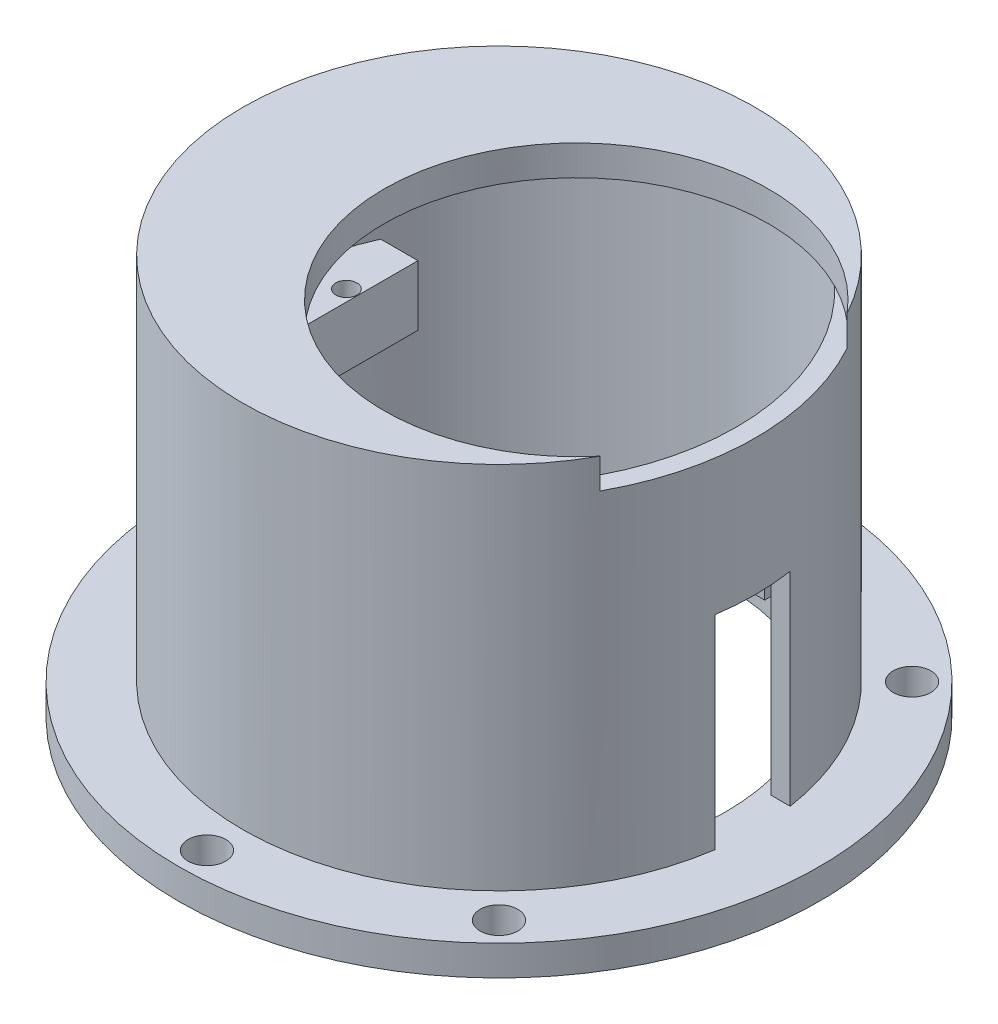
SolidWorks part; units mm, degrees
ref_plane "Front Plane" through (0, 0, 0) normal (0, 0, 1) x (1, 0, 0)
ref_plane "Top Plane" through (0, 0, 0) normal (0, 1, 0) x (1, 0, 0)
ref_plane "Right Plane" through (0, 0, 0) normal (1, 0, 0) x (0, 0, -1)
sketch "Sketch1" plane through (0, 0, 0) normal (0, 1, 0) x (1, 0, 0)
  circle A0 centre (0, 0) radius 30
  circle A1 centre (0, 0) radius 42.5
  dimension "D1" = 60
  dimension "D2" = 85
extrude "Boss-Extrude1" add sketch "Sketch1" along normal blind 4
sketch "Sketch2" plane through (0, 4, 0) normal (0, 1, 0) x (1, 0, 0)
  circle A3 centre (0, 0) radius 34
  circle A6 centre (0, 0) radius 31.5
  dimension "D1" = 63
extrude "Boss-Extrude2" add sketch "Sketch2" along normal blind 45
sketch "Sketch3" plane through (0, 0, 0) normal (0, 0, 1) x (1, 0, 0)
  line L0 (0, 0) -> (0, 49) construction
  line L1 (34, 49) -> (-34, 49) construction
  line L3 (22.25, 26) -> (30.25, 26)
  line L4 (22.25, 26) -> (22.25, 34)
  line L5 (22.25, 34) -> (30.25, 34)
  line L6 (30.25, 26) -> (30.25, 34)
  line L8 (42.5, 4) -> (-42.5, 4) construction
  line L9 (-31.25, 34) -> (-23.75, 34)
  line L10 (-31.25, 34) -> (-31.25, 26)
  line L11 (-31.25, 26) -> (-23.75, 26)
  line L12 (-23.75, 34) -> (-23.75, 26)
  dimension "D1" = 8
  dimension "D2" = 22.25
  dimension "D3" = 8
  dimension "D4" = 22
  dimension "D5" = 8
  dimension "D6" = 23.75
  dimension "D7" = 7.5
extrude "Boss-Extrude3" add sketch "Sketch3" along normal mid plane 26
sketch "Sketch4" plane through (22.25, 0, 0) normal (-1, 0, 0) x (0, 0, 1)
  line L0 (0, 26) -> (0, 34) construction
  line L1 (13, 26) -> (-13, 26) construction
  line L2 (13, 34) -> (-13, 34) construction
  line L4 (-5, 31) -> (5, 31)
  line L5 (-5, 31) -> (-5, 4)
  line L6 (-5, 4) -> (5, 4)
  line L7 (5, 31) -> (5, 4)
  line L8 (-5, 31) -> (5, 4) construction
  line L9 (-5, 4) -> (5, 31) construction
  point P6 (0, 17.5)
  dimension "D1" = 5
  dimension "D2" = 30
  dimension "D3" = 10
extrude "Cut-Extrude1" cut sketch "Sketch4" against normal through all
sketch "Sketch6" plane through (0, 34, 0) normal (0, 1, 0) x (1, 0, 0)
  line L0 (-25.25, 13) -> (-25.25, -13) construction
  line L1 (-23.75, 13) -> (-28.6923, 13) construction
  line L2 (-23.75, -13) -> (-28.6923, -13) construction
  line L3 (-23.75, -13) -> (-23.75, 13) construction
  line L4 (-25.25, 0) -> (23.75, 0) construction
  line L6 (23.75, -13) -> (23.75, 13)
  line L7 (28.6923, 13) -> (22.25, 13) construction
  circle A0 centre (-25.25, -5) radius 1.4
  circle A1 centre (23.75, -5) radius 1.4
  circle A2 centre (23.75, 5) radius 1.4
  circle A3 centre (-25.25, 5) radius 1.4
  point P15 (23.75, 0)
  dimension "D3" = 2.8
  dimension "D1" = 1.5
  dimension "D2" = 49
  dimension "D4" = 5
extrude "Cut-Extrude3" cut sketch "Sketch6" against normal blind 7.2 contours A3 | A2 | A1 | A0
sketch "Sketch8" plane through (0, 4, 0) normal (0, 1, 0) x (1, 0, 0)
  line L0 (0, 0) -> (30.4574, -30.4574) construction
  line L1 (0, 0) -> (0, -46.2977) construction
  line L2 (0, 0) -> (30.4574, 30.4574) construction
  circle A0 centre (0, 0) radius 38.75 construction
  circle A1 centre (-38.75, 0) radius 2.5
  circle A2 centre (0, 38.75) radius 2.5
  circle A4 centre (0, -38.75) radius 2.5
  circle A5 centre (27.4004, -27.4004) radius 2.5
  circle A6 centre (27.4004, 27.4004) radius 2.5
  point P13 (0, 0)
  dimension "D1" = 77.5
  dimension "D2" = 5
  dimension "D4" = 5
  dimension "D5" = 225
  dimension "D6" = 5
  dimension "D3" = 45
extrude "Cut-Extrude4" cut sketch "Sketch8" against normal up to surface (4 mm away) up to face at (0, 0, 42.5)
sketch "Sketch9" plane through (0, 49, 0) normal (0, 1, 0) x (1, 0, 0)
  circle A11 centre (10.25, 0) radius 25.5
  arc A12 (29.7957, 16.3773) -> (29.7957, -16.3773) centre (10.25, 0) ccw
  circle A14 centre (0, 0) radius 34
  arc A15 (29.7957, 16.3773) -> (29.7957, -16.3773) centre (0, 0) ccw
  dimension "D1" = 0.5
  dimension "D2" = 2.5
extrude "Boss-Extrude4" add sketch "Sketch9" along normal blind 4
